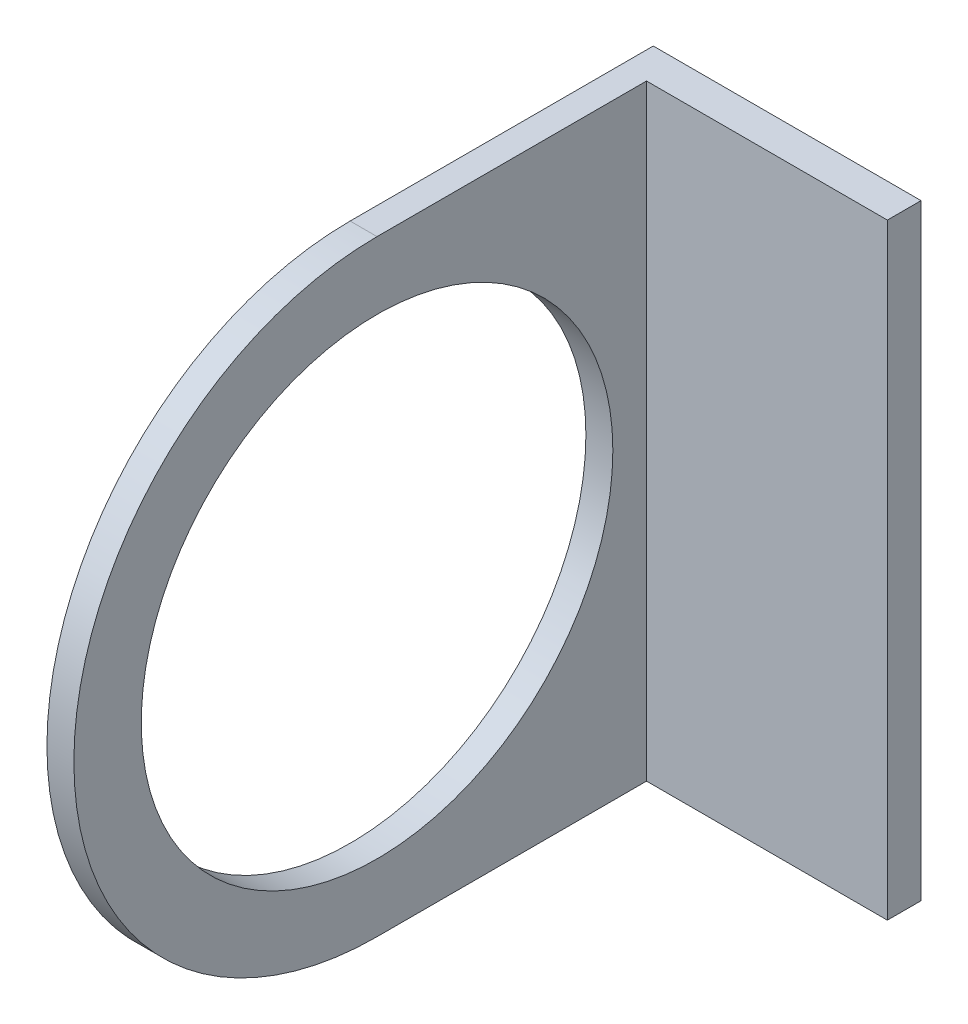
SolidWorks part; units mm, degrees
ref_plane "前视基准面" through (0, 0, 0) normal (0, 0, 1) x (1, 0, 0)
ref_plane "上视基准面" through (0, 0, 0) normal (0, 1, 0) x (1, 0, 0)
ref_plane "右视基准面" through (0, 0, 0) normal (1, 0, 0) x (0, 0, -1)
other "Configuration Table"
sketch "草图1" plane through (0, 0, 0) normal (0, 1, 0) x (1, 0, 0)
  line L0 (0, 0) -> (111.3, 0) construction
  line L1 (111.3, 0) -> (111.3, -10) construction
  line L2 (111.3, -10) -> (8, -10) construction
  line L3 (8, -10) -> (8, -300)
  line L4 (8, -300) -> (0, -300)
  line L5 (0, -300) -> (0, 0)
  line L6 (8, -10) -> (8, 0)
  line L7 (0, 0) -> (8, 0)
  dimension "D1" = 103.3
  dimension "D2" = 290
  dimension "D3" = 10
  dimension "D4" = 8
extrude "凸台-拉伸1" add sketch "草图1" along normal blind 180
sketch "草图2" plane through (8, 0, 0) normal (1, 0, 0) x (0, 0, -1)
  line L0 (-318.0541, 90) -> (-40.874, 90) construction
  line L1 (-300, 180) -> (0, 180) construction
  line L2 (-300, 0) -> (0, 0) construction
  line L3 (-90, 0) -> (-300, 0)
  line L4 (-300, 0) -> (-300, 180)
  line L5 (-300, 180) -> (-90, 180)
  line L7 (0, 180) -> (0, 0) construction
  arc A0 (-90, 180) -> (-90, 0) centre (-90, 90) ccw
  circle A1 centre (-90, 90) radius 70
  dimension "D2" = 140
  dimension "D1" = 90
extrude "切除-拉伸1" cut sketch "草图2" against normal blind 180
sketch "草图3" plane through (0, 0, 0) normal (-1, 0, 0) x (0, 0, 1)
  line L0 (0, 180) -> (-33.4481, 357.3687)
  line L1 (-33.4481, 357.3687) -> (29.1955, 395.566)
  line L3 (314.9515, 286.8152) -> (195.3561, -42.9636)
  line L4 (195.3561, -42.9636) -> (80.5757, -102.6908)
  line L6 (0, 0) -> (90, 0) construction
  line L7 (0, 180) -> (90, 180) construction
  line L8 (0, 0) -> (90, 0)
  line L9 (0, 180) -> (90, 180)
  line L10 (314.9515, 286.8152) -> (208.8377, 400.6164)
  line L11 (208.8377, 400.6164) -> (29.1955, 395.566)
  line L12 (0, 0) -> (0, -45.3218)
  line L13 (0, -45.3218) -> (80.5757, -102.6908)
  arc A0 (90, 0) -> (90, 180) centre (90, 90) ccw construction
  arc A1 (90, 0) -> (90, 180) centre (90, 90) ccw
  dimension "D12" = 45.3218
extrude "凸台-拉伸2" [suppressed] add sketch "草图3" against normal up to surface (8 mm away) up to face at (8, 90, 20)
fillet "圆角1" [suppressed] radius 50
sketch "草图4" [suppressed] plane through (8, 0, 0) normal (1, 0, 0) x (0, 0, -1)
  line L0 (0.866, 184.5924) -> (27.0434, 323.406) construction
  circle A0 centre (-205.8488, 391.166) radius 2.5
  circle A1 centre (-302.1195, 281.0491) radius 2.5
  circle A2 centre (-251.4598, 126.4058) radius 2.5
  circle A3 centre (-190.211, -35.6154) radius 2.5
  circle A4 centre (-79.8053, -88.9483) radius 2.5
  circle A5 centre (-30, 5.5773) radius 2.5
  circle A6 centre (-30, 202.0587) radius 2.5
  circle A7 centre (-30, 170.5483) radius 2.5
  circle A8 centre (-30, -11.97) radius 2.5
  circle A9 centre (14.8828, 358.3226) radius 2.5
  circle A10 centre (13.7706, 280.004) radius 2.5
  circle A11 centre (0.7986, 211.2164) radius 2.5
  circle A16 centre (-32.61, 32.4852) radius 2.5
  circle A17 centre (-16.3252, 55.7423) radius 2.5
  circle A18 centre (-32.4852, 147.39) radius 2.5
  dimension "D1" = 5
  dimension "D2" = 5
  dimension "D4" = 70
extrude "切除-拉伸2" [suppressed] cut sketch "草图4" against normal blind 40
sketch "草图5" plane through (8, 0, 0) normal (1, 0, 0) x (0, 0, -1)
  line L0 (-90, 0) -> (0, 0) construction
  line L1 (0, 180) -> (-10, 180)
  line L2 (0, 180) -> (0, 0)
  line L3 (0, 0) -> (-10, 0)
  line L4 (-10, 180) -> (-10, 0)
  dimension "D1" = 10
extrude "凸台-拉伸3" add sketch "草图5" along normal blind 71.5
